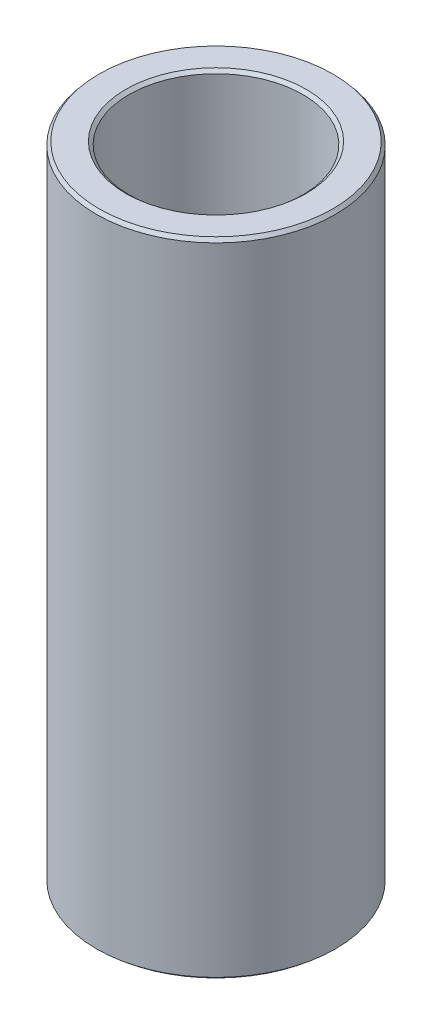
SolidWorks part; units mm, degrees
ref_plane "Front Plane" through (0, 0, 0) normal (0, 0, 1) x (1, 0, 0)
ref_plane "Top Plane" through (0, 0, 0) normal (0, 1, 0) x (1, 0, 0)
ref_plane "Right Plane" through (0, 0, 0) normal (1, 0, 0) x (0, 0, -1)
sketch "Sketch1" plane through (0, 0, 0) normal (0, 1, 0) x (1, 0, 0)
  circle A0 centre (0, 0) radius 35
  dimension "SLEEVE_OD" = 70
extrude "Boss-Extrude1" add sketch "Sketch1" along normal blind 187.8424
sketch "Sketch2" plane through (0, 0, 0) normal (0, 1, 0) x (1, 0, 0)
  circle A0 centre (0, 0) radius 25.4181
  dimension "BORE_D" = 50.8363
extrude "Cut-Extrude1" cut sketch "Sketch2" along normal through all
chamfer "Chamfer1" distance 0.9746 angle 40.375 4 edges at (0, 187.8424, 25.4181) (0, 0, 25.4181) (0, 0, 35) (0, 187.8424, 35) first distance on face at (0, 187.8424, 25.4181) first distance on face at (0, 0, 25.4181) first distance on face at (0, 187.8424, 35)
